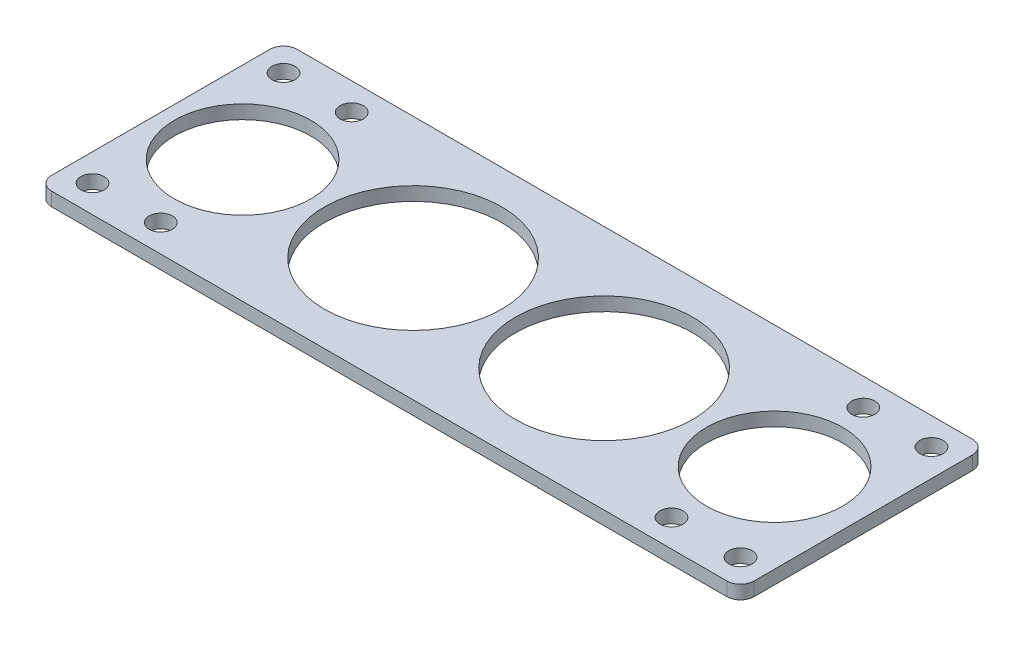
SolidWorks part; units mm, degrees
ref_plane "Front Plane" through (0, 0, 0) normal (0, 0, 1) x (1, 0, 0)
ref_plane "Top Plane" through (0, 0, 0) normal (0, 1, 0) x (1, 0, 0)
ref_plane "Right Plane" through (0, 0, 0) normal (1, 0, 0) x (0, 0, -1)
sketch "Sketch2" plane through (0, 0, 0) normal (0, 1, 0) x (1, 0, 0)
  line L3 (-50.1915, 20.4286) -> (52.8085, 20.4286)
  line L4 (-50.1915, 20.4286) -> (-50.1915, -15.5714)
  line L5 (-50.1915, -15.5714) -> (52.8085, -15.5714)
  line L6 (52.8085, 20.4286) -> (52.8085, -15.5714)
  circle A0 centre (-46.1915, 16.4286) radius 1.7
  circle A1 centre (-46.1915, -11.5714) radius 1.7
  circle A2 centre (48.8085, 16.4286) radius 1.7
  circle A3 centre (48.8085, -11.5714) radius 1.7
  circle A6 centre (14.8085, 2.4286) radius 13
  circle A7 centre (-36.1915, 16.4286) radius 1.7
  circle A8 centre (-36.1915, -11.5714) radius 1.7
  circle A9 centre (38.8085, 16.4286) radius 1.7
  circle A10 centre (38.6904, -11.5714) radius 1.7
  circle A11 centre (-13.1915, 2.4286) radius 13
  circle A12 centre (-38.1915, 2.4286) radius 10
  circle A13 centre (39.8085, 2.4286) radius 10
  dimension "D1" = 95
  dimension "D3" = 95
  dimension "D4" = 4
  dimension "D6" = 4
  dimension "D9" = 34
  dimension "D11" = 75
  dimension "D15" = 28
  dimension "D2" = 28
  dimension "D5" = 4
  dimension "D7" = 4
  dimension "D8" = 4
  dimension "D10" = 14
  dimension "D12" = 28
  dimension "D13" = 28
  dimension "D14" = 10
  dimension "D16" = 25
  dimension "D17" = 25
extrude "Boss-Extrude1" add sketch "Sketch2" along normal blind 2
fillet "Fillet1" radius 2 4 edges at (52.8085, 1, -20.4286) (52.8085, 1, 15.5714) (-50.1915, 1, -20.4286) (-50.1915, 1, 15.5714)
